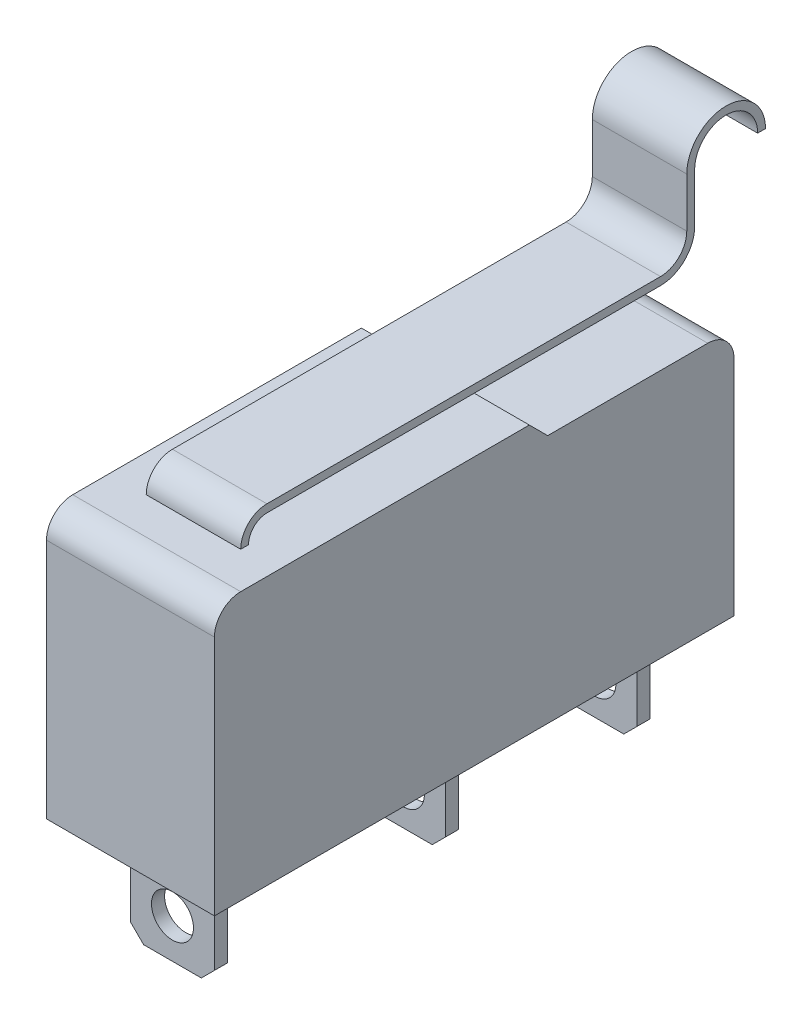
SolidWorks part; units mm, degrees
ref_plane "正面" through (0, 0, 0) normal (0, 0, 1) x (1, 0, 0)
ref_plane "平面" through (0, 0, 0) normal (0, 1, 0) x (1, 0, 0)
ref_plane "右側面" through (0, 0, 0) normal (1, 0, 0) x (0, 0, -1)
sketch "ｽｹｯﾁ1" plane through (0, 0, 0) normal (1, 0, 0) x (0, 0, -1)
  line L0 (12, 10.2) -> (12.7, 9.5)
  line L1 (0, 0) -> (19.8, 0)
  line L2 (0, 0) -> (0, 9.2)
  line L3 (12.7, 9.5) -> (18.8, 9.5)
  line L4 (19.8, 0) -> (19.8, 8.5)
  line L7 (1, 10.2) -> (12, 10.2)
  arc A0 (18.8, 9.5) -> (19.8, 8.5) centre (18.8, 8.5) cw
  arc A1 (0, 9.2) -> (1, 10.2) centre (1, 9.2) cw
  point P7 (19.8, 9.5)
  dimension "D3" = 1
  dimension "D5" = 1
  dimension "D1" = 19.8
  dimension "D2" = 9.5
  dimension "D4" = 10.2
  dimension "D6" = 12
  dimension "D7" = 135
extrude "ﾎﾞｽ - 押し出し1" add sketch "ｽｹｯﾁ1" along normal mid plane 6.4
sketch "ｽｹｯﾁ2" plane through (0, 0, 0) normal (1, 0, 0) x (0, 0, -1)
  line L0 (12, 10.2) -> (1, 10.2) construction
  line L1 (3.4, 11.2) -> (18.4, 11.2)
  line L2 (19.4, 12.2) -> (19.4, 14.0822)
  line L3 (3.4, 10.9) -> (18.4, 10.9)
  line L4 (19.7, 12.2) -> (19.7, 14.0822)
  line L5 (2.4, 10.2) -> (2.7, 10.2)
  line L6 (22.1, 14.0822) -> (22.4, 14.0822)
  line L7 (0, 9.2) -> (0, 0) construction
  line L9 (0, 0) -> (19.8, 0) construction
  arc A0 (2.4, 10.2) -> (3.4, 11.2) centre (3.4, 10.2) cw
  arc A1 (19.4, 14.0822) -> (22.4, 14.0822) centre (20.9, 14.0822) cw
  arc A2 (18.4, 11.2) -> (19.4, 12.2) centre (18.4, 12.2) ccw
  arc A3 (2.7, 10.2) -> (3.4, 10.9) centre (3.4, 10.2) cw
  arc A4 (18.4, 10.9) -> (19.7, 12.2) centre (18.4, 12.2) ccw
  arc A5 (19.7, 14.0822) -> (22.1, 14.0822) centre (20.9, 14.0822) cw
  arc A6 (19.4, 14.0822) -> (22.4, 14.0822) centre (20.9, 14.0822) cw construction
  point P22 (20.9, 15.5822)
  dimension "D1" = 1
  dimension "D5" = 1
  dimension "D6" = 1.5
  dimension "D3" = 20.9
  dimension "D4" = 15.5822
  dimension "D7" = 15
  dimension "D2" = 0.3
extrude "ﾎﾞｽ - 押し出し2" add sketch "ｽｹｯﾁ2" along normal mid plane 3.6
sketch "ｽｹｯﾁ3" plane through (0, 0, 0) normal (1, 0, 0) x (0, 0, -1)
  line L0 (0, 0) -> (19.8, 0) construction
  line L1 (1.6, 0) -> (2.1, 0)
  line L2 (1.6, 0) -> (1.6, -3.9)
  line L3 (1.6, -3.9) -> (2.1, -3.9)
  line L4 (2.1, 0) -> (2.1, -3.9)
  line L5 (0, 9.2) -> (0, 0) construction
  line L6 (10.4, 0) -> (10.9, 0)
  line L7 (10.4, 0) -> (10.4, -3.9)
  line L8 (10.4, -3.9) -> (10.9, -3.9)
  line L9 (10.9, 0) -> (10.9, -3.9)
  line L10 (17.7, 0) -> (18.2, 0)
  line L11 (17.7, 0) -> (17.7, -3.9)
  line L12 (17.7, -3.9) -> (18.2, -3.9)
  line L13 (18.2, 0) -> (18.2, -3.9)
  dimension "D1" = 0.5
  dimension "D2" = 3.9
  dimension "D3" = 1.6
  dimension "D4" = 8.8
  dimension "D5" = 7.3
extrude "ﾎﾞｽ - 押し出し3" add sketch "ｽｹｯﾁ3" along normal mid plane 3.2
chamfer "面取り1" distance 0.5 angle 45 6 edges at (-1.6, -3.9, -17.95) (-1.6, -3.9, -10.65) (-1.6, -3.9, -1.85) (1.6, -3.9, -17.95) (1.6, -3.9, -10.65) (1.6, -3.9, -1.85)
sketch "ｽｹｯﾁ4" plane through (0, 0, -18.2) normal (0, 0, -1) x (-1, 0, 0)
  line L0 (0, 0) -> (0, -3.9) construction
  line L1 (-1.1, -3.9) -> (1.1, -3.9) construction
  circle A0 centre (0, -2.4) radius 0.8
  dimension "D1" = 1.6
  dimension "D2" = 1.5
extrude "ｶｯﾄ - 押し出し1" cut sketch "ｽｹｯﾁ4" against normal through all
